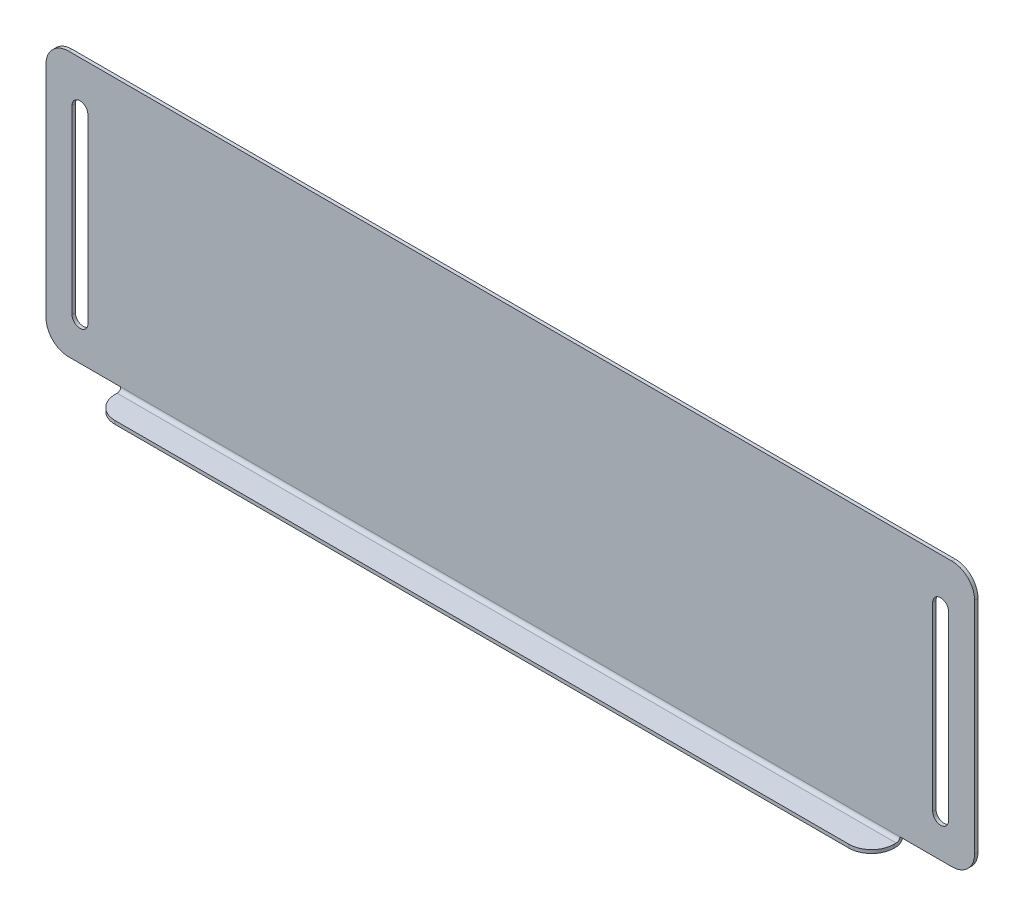
SolidWorks part; units mm, degrees
note: The reader was unsure of these and kept them because the rebuilt part matched: flange length of "Ребро-кромка1".
ref_plane "Спереди" through (0, 0, 0) normal (0, 0, 1) x (1, 0, 0)
ref_plane "Сверху" through (0, 0, 0) normal (0, 1, 0) x (1, 0, 0)
ref_plane "Справа" through (0, 0, 0) normal (1, 0, 0) x (0, 0, -1)
sketch "Эскиз1" plane through (0, 0, 0) normal (0, 0, 1) x (1, 0, 0)
  line L1 (-205, -60) -> (205, -60)
  line L2 (-205, -60) -> (-205, 60)
  line L3 (-205, 60) -> (205, 60)
  line L4 (205, -60) -> (205, 60)
  line L5 (-205, -60) -> (205, 60) construction
  line L6 (-205, 60) -> (205, -60) construction
  point P0 (0, 0)
  dimension "D1" = 410
  dimension "D2" = 120
base flange "Базовая кромка1" sketch "Эскиз1" thickness 1.5 reverse thickness direction no parameters "D1"=1.6
edge flange "Ребро-кромка1" sketch "Эскиз6" flange angle 90 flange length 14 flange position material inside bend radius 1.6 thickness 1.5 relief rectangular parameters "D6"=10, "D8"=0.2
sketch "Эскиз6" plane through (0, -60, 0) normal (0, -1, 0) x (1, 0, 0)
  line L0 (-205, 0) -> (205, 0) construction
  line L1 (-205, 0) -> (205, 0)
  line L2 (-205, 0) -> (-205, 12.5)
  line L3 (-205, 12.5) -> (205, 12.5)
  line L4 (205, 12.5) -> (205, 0)
bend "EdgeBend1" bend radius 1.6 bend angle 90 parameters "D5"=1
sketch "Эскиз8" plane through (0, -60, 0) normal (0, 1, 0) x (1, 0, 0)
  line L1 (-205, 1.5) -> (-172, 1.5)
  line L2 (-205, 1.5) -> (-205, -12.5)
  line L3 (-205, -12.5) -> (-172, -12.5)
  line L4 (-172, 1.5) -> (-172, -12.5)
  line L5 (0, 0) -> (0, -104.1721) construction
  line L6 (172, 1.5) -> (172, -12.5)
  line L7 (205, -12.5) -> (172, -12.5)
  line L8 (205, 1.5) -> (205, -12.5)
  line L9 (205, 1.5) -> (172, 1.5)
  line L10 (205, -12.5) -> (-205, -12.5) construction
  dimension "D1" = 33
extrude "Вырез-Вытянуть1" cut sketch "Эскиз8" along normal up to vertex
fillet "Скругление2" radius 10 6 edges at (-172, -59.25, 12.5) (-205, -56.9, -0.75) (172, -59.25, 12.5) (205, -56.9, -0.75) (205, 60, -0.75) (-205, 60, -0.75)
sketch "Эскиз13" plane through (0, 0, 0) normal (0, 0, 1) x (1, 0, 0)
  line L0 (-190, 40) -> (-190, -40) construction
  line L1 (-186.5, 40) -> (-186.5, -40)
  line L2 (-193.5, 40) -> (-193.5, -40)
  line L4 (0, 0) -> (0, 148.9803) construction
  line L5 (190, 40) -> (190, -40) construction
  line L6 (186.5, 40) -> (186.5, -40)
  line L7 (193.5, 40) -> (193.5, -40)
  arc A0 (-186.5, 40) -> (-193.5, 40) centre (-190, 40) ccw
  arc A1 (-193.5, -40) -> (-186.5, -40) centre (-190, -40) ccw
  arc A2 (186.5, 40) -> (193.5, 40) centre (190, 40) cw
  arc A3 (193.5, -40) -> (186.5, -40) centre (190, -40) cw
  point P2 (-190, 0)
  point P12 (190, 0)
  dimension "D1" = 7
  dimension "D2" = 380
  dimension "D3" = 80
extrude "Вырез-Вытянуть3" cut sketch "Эскиз13" against normal blind 10
sketch "Сгиб-Линии1" [suppressed] plane through (0, 0, 0) normal (0, 1, 0) x (1, 0, 0)
sketch "Граничная рамка1" [suppressed] plane through (0, 0, 0) normal (0, 1, 0) x (1, 0, 0)
sheet metal parameters "Листовой металл3" thickness 1.5 parameters "D1"=0.7366
flat pattern "Развертка3" [suppressed]
sketch "Сгиб-Линии2" plane through (0, 0, 0) normal (0, 1, 0) x (1, 0, 0)
sketch "Граничная рамка2" [suppressed] plane through (0, 0, 0) normal (0, 1, 0) x (1, 0, 0)
sheet metal parameters "Листовой металл10" thickness 1.5 parameters "D1"=0.7366
flat pattern "Развертка3" [suppressed]
sketch "Сгиб-Линии2" plane through (0, 0, 0) normal (0, 1, 0) x (1, 0, 0)
sketch "Граничная рамка2" [suppressed] plane through (0, 0, 0) normal (0, 1, 0) x (1, 0, 0)
bend of the flat pattern "Плоское состояние-<EdgeBend1>1"
sheet metal parameters "Листовой металл11" thickness 1.5 parameters "D1"=0.7366
flat pattern "Развертка3" [suppressed]
sketch "Сгиб-Линии2" plane through (0, 0, 0) normal (0, 1, 0) x (1, 0, 0)
sketch "Граничная рамка2" [suppressed] plane through (0, 0, 0) normal (0, 1, 0) x (1, 0, 0)
bend of the flat pattern "Плоское состояние-<EdgeBend1>1"
sheet metal parameters "Листовой металл15" thickness 1.5 parameters "D1"=0.7366
flat pattern "Развертка3"
sketch "Сгиб-Линии2" plane through (0, 0, 0) normal (0, 0, 1) x (1, 0, 0)
  line L0 (-172, -58.6279) -> (172, -58.6279) construction
  line L1 (-172, -58.6279) -> (172, -58.6279) construction
sketch3d "Граничная рамка2" [suppressed]
  line L0 (-205, -71.2558, 0) -> (205, -71.2558, 0) construction
  line L1 (-205, 60, 0) -> (205, 60, 0) construction
  line L2 (-205, -71.2558, 0) -> (-205, 60, 0) construction
  line L3 (205, -71.2558, 0) -> (205, 60, 0) construction
bend of the flat pattern "Плоское состояние-<EdgeBend1>1"
